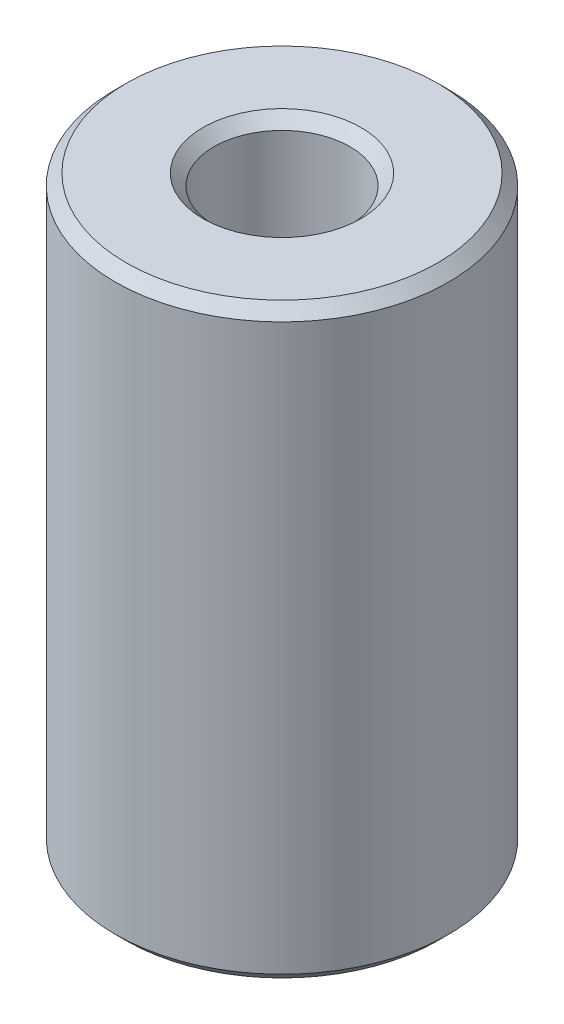
SolidWorks part; units mm, degrees
ref_plane "Front Plane" through (0, 0, 0) normal (0, 0, 1) x (1, 0, 0)
ref_plane "Top Plane" through (0, 0, 0) normal (0, 1, 0) x (1, 0, 0)
ref_plane "Right Plane" through (0, 0, 0) normal (1, 0, 0) x (0, 0, -1)
sketch "Sketch1" plane through (0, 0, 0) normal (0, 1, 0) x (1, 0, 0)
  circle A0 centre (0, 0) radius 55
  dimension "SLEEVE_OD" = 110
extrude "Boss-Extrude1" add sketch "Sketch1" along normal blind 193.6894
sketch "Sketch2" plane through (0, 0, 0) normal (0, 1, 0) x (1, 0, 0)
  circle A0 centre (0, 0) radius 22.4194
  dimension "BORE_D" = 44.8387
extrude "Cut-Extrude1" cut sketch "Sketch2" along normal through all
chamfer "Chamfer1" distance 3.6487 angle 45 4 edges at (0, 193.6894, 22.4194) (0, 0, 22.4194) (0, 0, 55) (0, 193.6894, 55)
